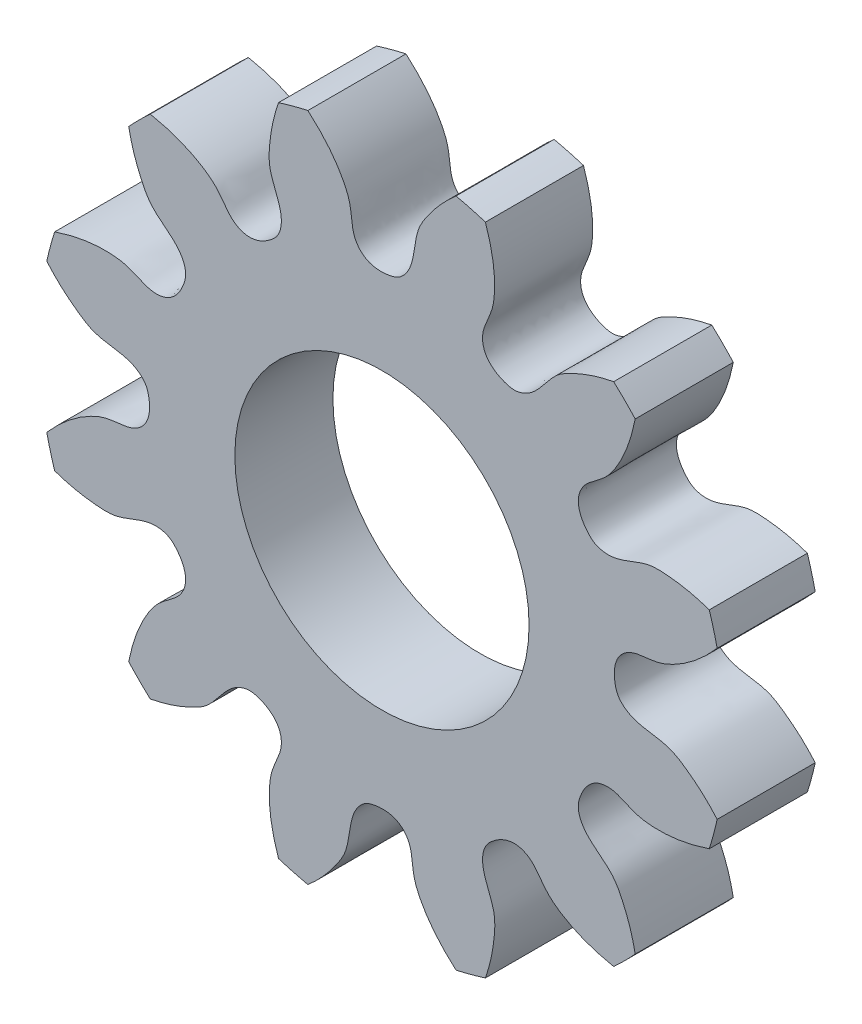
SolidWorks part; units mm, degrees
ref_plane "Front" through (0, 0, 0) normal (0, 0, 1) x (1, 0, 0)
ref_plane "Top" through (0, 0, 0) normal (0, 1, 0) x (1, 0, 0)
ref_plane "Right" through (0, 0, 0) normal (1, 0, 0) x (0, 0, -1)
ref_axis "Axis1" through (0, 0, 50) along (0, 0, -1)
sketch "SketchRevolveN12_encoder" plane through (0, 0, 0) normal (1, 0, 0) x (0, 0, -1)
  line L0 (0, 0) -> (1, 0) construction
  line L1 (-1, 0) -> (-1, 7)
  line L2 (-1, 7) -> (1, 7)
  line L3 (1, 7) -> (1, 0)
  line L4 (1, 0) -> (-1, 0)
  dimension "Side1" = 1
  dimension "OutsideRadius" = 7
  dimension "Side2" = 1
revolve "N12_encoder" add sketch "SketchRevolveN12_encoder" angle 360 about L0
sketch "SketchToothN12_encoder" plane through (0, 0, 0) normal (0, 0, 1) x (1, 0, 0)
  arc A0 (6.8758, 1.5574) -> (6.8758, -1.5574) centre (0, 0) cw
  spline S0 degree 3 poles (6.8758, -1.5574) (6.7524, -1.4121) (6.539, -1.1904) (6.2056, -0.9342) (5.8293, -0.6848) (5.4222, -0.6722) (5.0907, -0.5746) (4.924, -0.4725) (4.794, -0.3296) (4.7349, -0.0976) (4.7315, 0.1518) (4.8348, 0.3972) (5.1219, 0.6332) (5.5566, 0.6028) (6.225, 0.8947) (6.6187, 1.2547) (6.8758, 1.5574) knots 0 0 0 0 0.101357 0.162594 0.224534 0.336345 0.376288 0.407095 0.439691 0.476365 0.533171 0.568792 0.616016 0.721305 0.788839 1 1 1 1
extrude "ToothExtrudeCutN12_encoder" cut sketch "SketchToothN12_encoder" against normal blind 1 and the other way blind 1
pattern_circular "PatternN12_encoder" count 12 over 360 about axis through (0, 0, 50) along (0, 0, -1) of "ToothExtrudeCutN12_encoder"
sketch "BoreRevolveSketch" plane through (0, 0, 0) normal (1, 0, 0) x (0, 0, -1)
  line L0 (0, 0) -> (1, 0) construction
  line L1 (-1, 0) -> (1, 0)
  line L2 (1, 0) -> (1, 3)
  line L3 (1, 3) -> (-1, 3)
  line L4 (-1, 3) -> (-1, 0)
  dimension "BoreSide1" = 1
  dimension "TaperSide1" = 3
  dimension "BoreSide2" = 1
  dimension "TaperSide2" = 3
revolve "BoreRevolveCut" cut sketch "BoreRevolveSketch" angle 360 about L0
